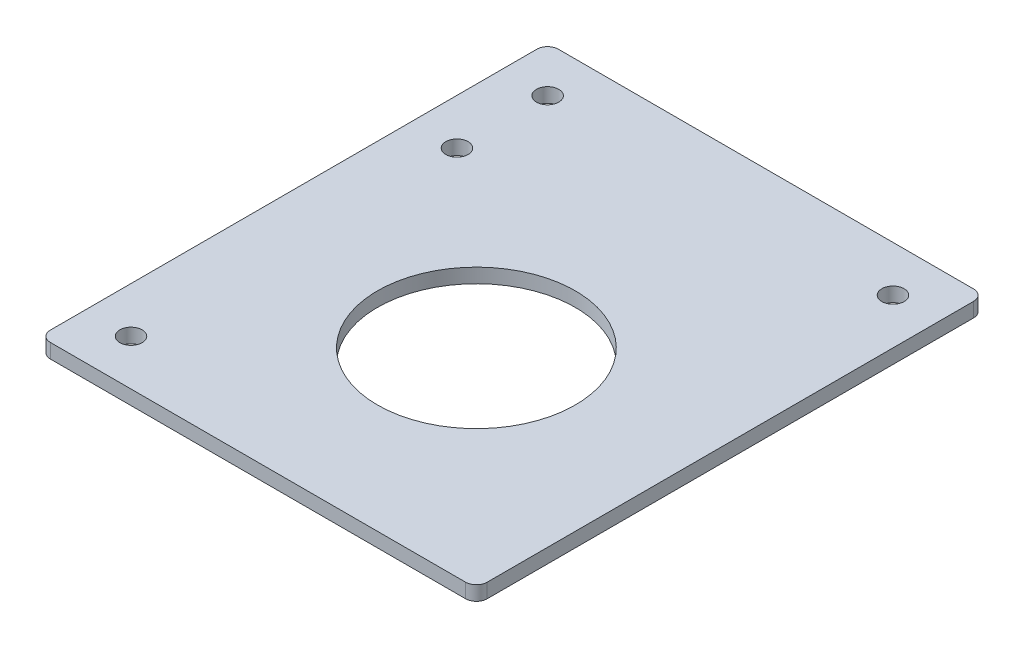
SolidWorks part; units mm, degrees
ref_plane "Front Plane" through (0, 0, 0) normal (0, 0, 1) x (1, 0, 0)
ref_plane "Top Plane" through (0, 0, 0) normal (0, 1, 0) x (1, 0, 0)
ref_plane "Right Plane" through (0, 0, 0) normal (1, 0, 0) x (0, 0, -1)
sketch "Sketch1" plane through (0, 0, 0) normal (0, 1, 0) x (1, 0, 0)
  line L0 (0.7175, -90.4) -> (88.7175, -90.4) construction
  line L1 (0.7175, 25.4) -> (122.1175, 25.4)
  line L3 (0.7175, -115.8) -> (122.1175, -115.8)
  line L4 (122.1175, 25.4) -> (122.1175, -115.8)
  line L5 (-27.2825, -90.4) -> (88.7175, -90.4) construction
  line L6 (88.7175, -90.4) -> (96.7175, -82.4) construction
  line L7 (96.7175, -82.4) -> (96.7175, -33.4) construction
  line L12 (96.7175, -33.4) -> (88.7175, -25.4) construction
  line L13 (88.7175, -25.4) -> (0.7175, -25.4) construction
  line L14 (88.7175, -25.4) -> (-27.2825, -25.4) construction
  line L16 (13.4175, 12.7) -> (0.7175, 12.7) construction
  line L17 (13.4175, 12.7) -> (13.4175, 25.4) construction
  line L18 (109.4175, 12.7) -> (109.4175, 25.4) construction
  line L19 (109.4175, 12.7) -> (122.1175, 12.7) construction
  line L20 (13.4175, -103.1) -> (0.7175, -103.1) construction
  line L21 (13.4175, -103.1) -> (13.4175, -100) construction
  line L22 (13.4175, -103.1) -> (13.4175, -115.8) construction
  line L23 (13.4175, 12.7) -> (16.5175, 12.7) construction
  line L24 (0.7175, -35.9) -> (16.9175, -35.9) construction
  line L25 (109.4175, 12.7) -> (109.4175, 9.6) construction
  line L30 (0.7175, 25.4) -> (0.7175, -115.8)
  line L31 (16.9175, -35.9) -> (-25.2825, -35.9) construction
  line L32 (13.4175, 12.7) -> (13.4175, -12.5) construction
  line L35 (-25.2825, -39.9) -> (16.9175, -39.9) construction
  line L36 (0.7175, -39.9) -> (16.9175, -39.9) construction
  line L37 (13.4175, -12.5) -> (16.5175, -12.5) construction
  circle A0 centre (64.2175, -57.9) radius 27.5
  circle A1 centre (13.4175, 12.7) radius 3.1
  circle A2 centre (109.4175, 12.7) radius 3.1
  circle A4 centre (13.4175, -103.1) radius 3.1
  arc A5 (16.9175, -39.9) -> (16.9175, -35.9) centre (16.9175, -37.9) ccw construction
  circle A6 centre (13.4175, -12.5) radius 3.1
  dimension "D4" = 55
  dimension "D5" = 88
  dimension "D6" = 6.2
  dimension "D1" = 50.8
  dimension "D2" = 25.4
  dimension "D3" = 25.4
  dimension "D7" = 12.7
  dimension "D8" = 25.2
extrude "Boss-Extrude1" add sketch "Sketch1" along normal blind 4
fillet "Fillet1" radius 3 4 edges at (122.1175, 2, -25.4) (122.1175, 2, 115.8) (0.7175, 2, 115.8) (0.7175, 2, -25.4)
